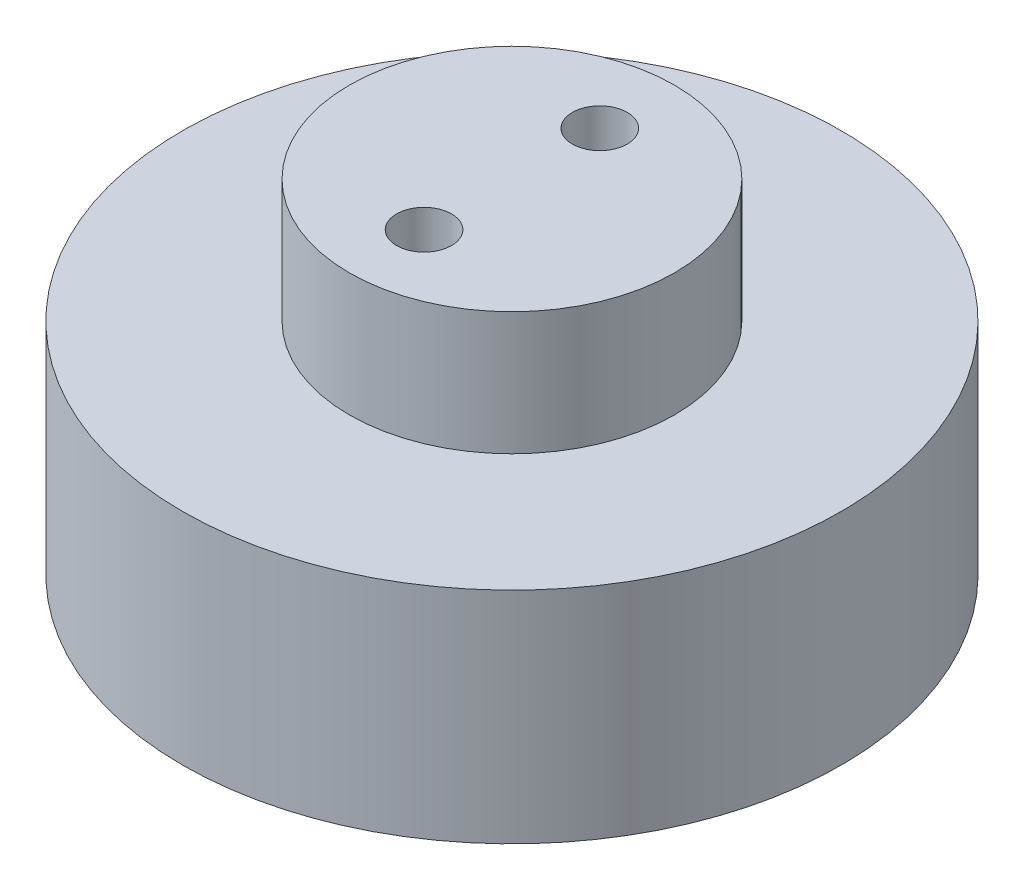
SolidWorks part; units mm, degrees
ref_plane "Front Plane" through (0, 0, 0) normal (0, 0, 1) x (1, 0, 0)
ref_plane "Top Plane" through (0, 0, 0) normal (0, 1, 0) x (1, 0, 0)
ref_plane "Right Plane" through (0, 0, 0) normal (1, 0, 0) x (0, 0, -1)
sketch "Sketch1" plane through (0, 0, 0) normal (0, 1, 0) x (1, 0, 0)
  circle A0 centre (0, 0) radius 19.05
  dimension "D1" = 38.1
extrude "Boss-Extrude1" add sketch "Sketch1" along normal blind 12.7
sketch "Sketch2" plane through (0, 12.7, 0) normal (0, 1, 0) x (1, 0, 0)
  circle A0 centre (0, 0) radius 9.398
  dimension "D1" = 18.796
extrude "Boss-Extrude2" add sketch "Sketch2" along normal blind 7.112
sketch "Sketch3" plane through (0, 0, 0) normal (0, -1, 0) x (1, 0, 0)
  circle A0 centre (0, 0) radius 2.921
  dimension "D1" = 5.842
extrude "Cut-Extrude1" [suppressed] cut sketch "Sketch3" against normal blind 17.272
sketch "Sketch4" [suppressed] plane through (0, 17.272, 0) normal (0, -1, 0) x (-1, 0, 0)
  circle A0 centre (0, 0) radius 1.5875
extrude "Cut-Extrude2" [suppressed] cut sketch "Sketch4" against normal blind 17.78
sketch "Sketch5" plane through (0, 0, 0) normal (0, -1, 0) x (1, 0, 0)
  line L1 (-5.394, 0) -> (-7.777, 4.1275)
  line L2 (-7.777, 4.1275) -> (-12.543, 4.1275)
  line L3 (-12.543, 4.1275) -> (-14.926, 0)
  line L4 (-14.926, 0) -> (-12.543, -4.1275)
  line L5 (-12.543, -4.1275) -> (-7.777, -4.1275)
  line L6 (-7.777, -4.1275) -> (-5.394, 0)
  line L7 (14.926, 0) -> (12.543, 4.1275)
  line L8 (12.543, 4.1275) -> (7.777, 4.1275)
  line L9 (7.777, 4.1275) -> (5.394, 0)
  line L10 (5.394, 0) -> (7.777, -4.1275)
  line L11 (7.777, -4.1275) -> (12.543, -4.1275)
  line L12 (12.543, -4.1275) -> (14.926, 0)
  circle A0 centre (-10.16, 0) radius 4.1275 construction
  circle A1 centre (10.16, 0) radius 4.1275 construction
  dimension "D1" = 8.255
  dimension "D2" = 8.255
  dimension "D3" = 10.16
  dimension "D4" = 20.32
extrude "Cut-Extrude3" cut sketch "Sketch5" against normal blind 3.175
sketch "Sketch6" plane through (0, 0, 0) normal (0, -1, 0) x (1, 0, 0)
  circle A0 centre (-10.16, 0) radius 1.5875
  circle A1 centre (10.16, 0) radius 1.5875
  dimension "D2" = 3.175
  dimension "D3" = 20.32
  dimension "D4" = 10.16
extrude "Cut-Extrude4" cut sketch "Sketch6" against normal blind 7.62
sketch "Sketch7" plane through (0, 0, 0) normal (0, -1, 0) x (1, 0, 0)
  circle A0 centre (0, 5.08) radius 2.921
  circle A1 centre (0, -5.08) radius 2.921
  point P4 (0, 0)
  point P7 (0.1923, 4.6881)
  dimension "D1" = 5.842
  dimension "D2" = 5.842
  dimension "D3" = 5.08
  dimension "D4" = 10.16
extrude "Cut-Extrude5" cut sketch "Sketch7" against normal blind 17.272
sketch "Sketch8" plane through (0, 17.272, 0) normal (0, -1, 0) x (1, 0, 0)
  circle A0 centre (0, 5.08) radius 1.5875
  circle A1 centre (0, -5.08) radius 1.5875
  dimension "D1" = 3.175
  dimension "D2" = 3.175
extrude "Cut-Extrude6" cut sketch "Sketch8" against normal through all
